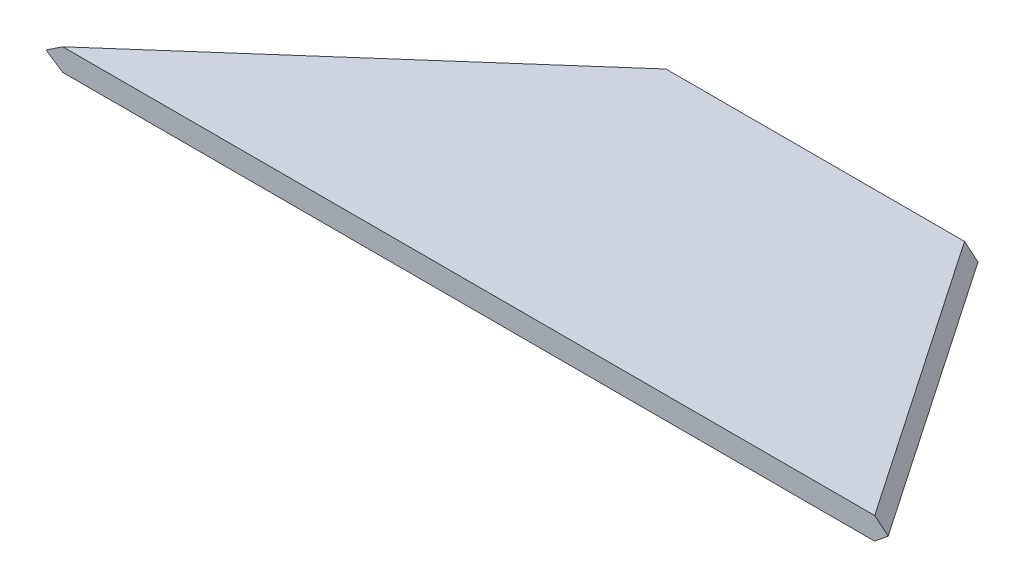
SolidWorks part; units mm, degrees
ref_plane "Front Plane" through (0, 0, 0) normal (0, 0, 1) x (1, 0, 0)
ref_plane "Top Plane" through (0, 0, 0) normal (0, 1, 0) x (1, 0, 0)
ref_plane "Right Plane" through (0, 0, 0) normal (1, 0, 0) x (0, 0, -1)
sketch "Sketch1" plane through (0, 0, 0) normal (0, 1, 0) x (1, 0, 0)
  line L0 (0, 0) -> (203.2, 0)
  line L1 (203.2, 0) -> (157.48, 67.056)
  line L2 (157.48, 67.056) -> (76.2, 67.056)
  line L3 (76.2, 67.056) -> (0, 0)
  dimension "D1" = 203.2
  dimension "D2" = 81.28
  dimension "D3" = 67.056
  dimension "D4" = 76.2
extrude "Boss-Extrude1" add sketch "Sketch1" along normal blind 5.2832
chamfer "Chamfer1" distance 3.81 angle 45 2 edges at (38.1, 5.2832, -33.528) (38.1, 0, -33.528)
chamfer "Chamfer2" distance 3.81 angle 45 2 edges at (180.34, 0, -33.528) (180.34, 5.2832, -33.528)
